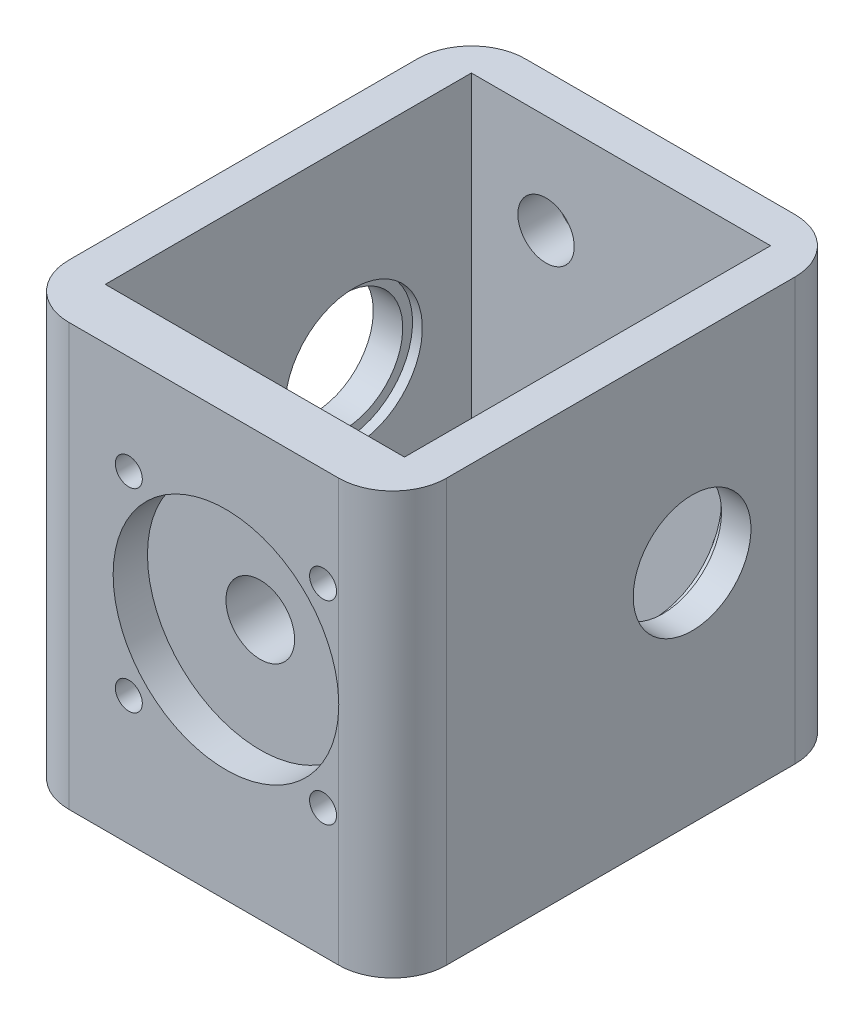
SolidWorks part; units mm, degrees
note: The reader was unsure of these and kept them because the rebuilt part matched: shared geometry of "Sketch4<3>", "Sketch4<4>", "Sketch4<5>", "Sketch6<3>", "Sketch6<4>".
ref_plane "Front Plane" through (0, 0, 0) normal (0, 0, 1) x (1, 0, 0)
ref_plane "Top Plane" through (0, 0, 0) normal (0, 1, 0) x (1, 0, 0)
ref_plane "Right Plane" through (0, 0, 0) normal (1, 0, 0) x (0, 0, -1)
sketch "Sketch1" plane through (0, 0, 0) normal (0, 1, 0) x (1, 0, 0)
  line L0 (-18, -30.53) -> (18, -30.53) construction
  line L1 (-3, -3.58) -> (3, -3.58) construction
  line L2 (-3, -3.58) -> (-3, -27.32) construction
  line L4 (3, -3.58) -> (3, -27.32) construction
  line L5 (-11, -27.32) -> (11, -27.32) construction
  line L6 (-11, -27.32) -> (-11, -30.53) construction
  line L8 (11, -27.32) -> (11, -30.53) construction
  line L13 (-6.58, 10.16) -> (-10.36, 10.16) construction
  line L14 (-10.16, -6.58) -> (10.16, -6.58) construction
  line L15 (-10.16, -6.58) -> (-10.16, -10.36) construction
  line L16 (-10.16, -10.36) -> (10.16, -10.36) construction
  line L17 (10.16, -6.58) -> (10.16, -10.36) construction
  line L18 (6.22, -10.36) -> (-6.22, -10.36) construction
  line L19 (6.22, -10.36) -> (6.22, -16.71) construction
  line L20 (6.22, -16.71) -> (-6.22, -16.71) construction
  line L21 (-6.22, -10.36) -> (-6.22, -16.71) construction
  line L22 (-6.58, 10.16) -> (-6.58, -10.16) construction
  line L23 (-6.58, -10.16) -> (-10.36, -10.16) construction
  line L24 (-10.36, 10.16) -> (-10.36, -10.16) construction
  line L25 (-10.36, -6.22) -> (-16.71, -6.22) construction
  line L26 (-10.36, -6.22) -> (-10.36, 6.22) construction
  line L27 (-10.36, 6.22) -> (-16.71, 6.22) construction
  line L28 (-16.71, -6.22) -> (-16.71, 6.22) construction
  line L37 (6.58, -10.16) -> (10.36, -10.16) construction
  line L38 (6.58, -10.16) -> (6.58, 10.16) construction
  line L39 (6.58, 10.16) -> (10.36, 10.16) construction
  line L40 (10.36, -10.16) -> (10.36, 10.16) construction
  line L41 (10.36, 6.22) -> (16.71, 6.22) construction
  line L42 (10.36, 6.22) -> (10.36, -6.22) construction
  line L43 (10.36, -6.22) -> (16.71, -6.22) construction
  line L44 (16.71, 6.22) -> (16.71, -6.22) construction
  line L45 (-18.51, -6) -> (-21.71, -6) construction
  line L46 (-6.8, -17.71) -> (6.8, -17.71) construction
  line L47 (-6.8, -17.71) -> (-6.8, -18.51) construction
  line L48 (-6.8, -18.51) -> (6.8, -18.51) construction
  line L49 (6.8, -17.71) -> (6.8, -18.51) construction
  line L50 (6, -18.51) -> (-6, -18.51) construction
  line L51 (6, -18.51) -> (6, -21.71) construction
  line L52 (6, -21.71) -> (-6, -21.71) construction
  line L53 (-6, -18.51) -> (-6, -21.71) construction
  line L54 (10.16, 6.58) -> (10.16, 10.36)
  line L55 (10.16, 6.58) -> (-10.16, 6.58)
  line L56 (-10.16, 6.58) -> (-10.16, 10.36)
  line L57 (10.16, 10.36) -> (-10.16, 10.36)
  line L58 (-6.22, 10.36) -> (-6.22, 16.71)
  line L59 (-6.22, 10.36) -> (6.22, 10.36)
  line L60 (6.22, 10.36) -> (6.22, 16.71)
  line L61 (-6.22, 16.71) -> (6.22, 16.71)
  line L62 (-18.51, -6) -> (-18.51, 6) construction
  line L63 (-18.51, 6) -> (-21.71, 6) construction
  line L64 (-21.71, -6) -> (-21.71, 6) construction
  line L65 (-17.71, 6.8) -> (-18.51, 6.8) construction
  line L66 (-17.71, 6.8) -> (-17.71, -6.8) construction
  line L67 (-17.71, -6.8) -> (-18.51, -6.8) construction
  line L68 (-18.51, 6.8) -> (-18.51, -6.8) construction
  line L77 (18.51, 6) -> (21.71, 6) construction
  line L78 (18.51, 6) -> (18.51, -6) construction
  line L79 (18.51, -6) -> (21.71, -6) construction
  line L80 (21.71, 6) -> (21.71, -6) construction
  line L81 (17.71, -6.8) -> (18.51, -6.8) construction
  line L82 (17.71, -6.8) -> (17.71, 6.8) construction
  line L83 (17.71, 6.8) -> (18.51, 6.8) construction
  line L84 (18.51, -6.8) -> (18.51, 6.8) construction
  line L85 (-6, 18.51) -> (-6, 21.71)
  line L86 (-6, 18.51) -> (6, 18.51)
  line L87 (6, 18.51) -> (6, 21.71)
  line L88 (-6, 21.71) -> (6, 21.71)
  line L89 (6.8, 17.71) -> (6.8, 18.51)
  line L90 (6.8, 17.71) -> (-6.8, 17.71)
  line L91 (-6.8, 17.71) -> (-6.8, 18.51)
  line L92 (6.8, 18.51) -> (-6.8, 18.51)
  line L93 (13.99, 6) -> (17.19, 6) construction
  line L94 (17.19, 6) -> (17.19, -6) construction
  line L95 (13.99, -6) -> (17.19, -6) construction
  line L96 (13.99, 6) -> (13.99, -6) construction
  line L97 (13.19, -6.8) -> (13.99, -6.8) construction
  line L98 (13.99, -6.8) -> (13.99, 6.8) construction
  line L99 (13.19, 6.8) -> (13.99, 6.8) construction
  line L100 (13.19, -6.8) -> (13.19, 6.8) construction
  line L101 (0, 0) -> (0, 17.1945) construction
  line L102 (-13.19, -6.8) -> (-13.19, 6.8) construction
  line L103 (-13.19, 6.8) -> (-13.99, 6.8) construction
  line L104 (-13.99, -6.8) -> (-13.99, 6.8) construction
  line L105 (-13.19, -6.8) -> (-13.99, -6.8) construction
  line L106 (-13.99, 6) -> (-13.99, -6) construction
  line L107 (-13.99, -6) -> (-17.19, -6) construction
  line L108 (-17.19, 6) -> (-17.19, -6) construction
  line L109 (-13.99, 6) -> (-17.19, 6) construction
  line L110 (-16, 16) -> (16, 16) construction
  circle A0 centre (0, 0) radius 4 construction
  circle A1 centre (8, 0) radius 1.85 construction
  circle A2 centre (5.6569, -5.6569) radius 1.85 construction
  circle A3 centre (0, -8) radius 1.85 construction
  circle A4 centre (-5.6569, -5.6569) radius 1.85 construction
  circle A5 centre (-8, 0) radius 1.85 construction
  circle A6 centre (-5.6569, 5.6569) radius 1.85 construction
  circle A7 centre (0, 8) radius 1.85 construction
  circle A8 centre (5.6569, 5.6569) radius 1.85 construction
  point P9 (0, -3.58)
  point P10 (0, -27.32)
  point P13 (0, -30.53)
  point P22 (0, -16.71)
  point P23 (0, -6.58)
  point P51 (0, 0)
  point P70 (0, 0)
  point P76 (0, -21.71)
  point P77 (0, -17.71)
  point P139 (0, 16)
  dimension "D13" = 8
  dimension "D14" = 3.7
  dimension "D1" = 36
  dimension "D2" = 22
  dimension "D3" = 6
  dimension "D4" = 3.21
  dimension "D5" = 26.95
  dimension "D6" = 3.58
  dimension "D7" = 3.78
  dimension "D8" = 6.35
  dimension "D9" = 20.32
  dimension "D10" = 12.44
  dimension "D11" = 20.17
  dimension "D12" = 4
  dimension "D15" = 8
  dimension "D17" = 0.8
  dimension "D18" = 3.2
  dimension "D19" = 13.6
  dimension "D20" = 12
  dimension "D21" = 1
  dimension "D23" = 19.77
  dimension "D24" = 16
  dimension "D25" = 16
  dimension "D22" = 2
  dimension "D16" = 8
sketch "Sketch3" plane through (0, 0, 0) normal (0, 1, 0) x (1, 0, 0)
  line L0 (-18, -30.53) -> (18, -30.53) construction
  line L1 (-16.01, 16) -> (11.49, 16)
  line L2 (-21.51, 10.5) -> (-21.51, -25.03)
  line L3 (-16.01, -30.53) -> (11.49, -30.53)
  line L4 (16.99, 10.5) -> (16.99, -25.03)
  line L7 (-16, 16) -> (16, 16) construction
  line L10 (13.99, -6.8) -> (13.99, 6.8) construction
  line L11 (-13.99, -6.8) -> (-13.99, 6.8) construction
  arc A0 (11.49, 16) -> (16.99, 10.5) centre (11.49, 10.5) cw
  arc A1 (11.49, -30.53) -> (16.99, -25.03) centre (11.49, -25.03) ccw
  arc A2 (-21.51, -25.03) -> (-16.01, -30.53) centre (-16.01, -25.03) ccw
  arc A3 (-16.01, 16) -> (-21.51, 10.5) centre (-16.01, 10.5) ccw
  dimension "D3" = 5.5
  dimension "D2" = 3
  dimension "D1" = 7.52
extrude "Boss-Extrude1" add sketch "Sketch3" along normal blind 20 and the other way blind 23
sketch "Sketch5" plane through (0, 20, 0) normal (0, 1, 0) x (1, 0, 0)
  line L0 (-21.51, 10.5) -> (-21.51, -25.03) construction
  line L1 (-17.51, 12) -> (12.99, 12)
  line L2 (-17.51, 12) -> (-17.51, -25.32)
  line L3 (-17.51, -25.32) -> (12.99, -25.32)
  line L4 (12.99, 12) -> (12.99, -25.32)
  line L5 (-11, -27.32) -> (11, -27.32) construction
  line L6 (-16, 16) -> (16, 16) construction
  line L7 (16.99, -25.03) -> (16.99, 10.5) construction
  dimension "D1" = 4
  dimension "D2" = 2
  dimension "D3" = 4
  dimension "D4" = 4
extrude "Cut-Extrude1" cut sketch "Sketch5" against normal offset from surface (40 mm away) 3 up to face at (-2.26, -23, 7.265)
sketch "Sketch4" plane through (0, 0, 25.32) normal (0, 0, 1) x (1, 0, 0)
  line L0 (-11.0781, 3.0864) -> (-17.51, -20)
  line L1 (-9.9, -9.9) -> (9.9, -9.9) construction
  line L2 (-9.9, -9.9) -> (-9.9, 9.9) construction
  line L3 (-9.9, 9.9) -> (9.9, 9.9) construction
  line L4 (9.9, -9.9) -> (9.9, 9.9) construction
  line L5 (-9.9, -9.9) -> (9.9, 9.9) construction
  line L6 (-9.9, 9.9) -> (9.9, -9.9) construction
  line L7 (11.4695, 0.8369) -> (12.99, -20)
  line L8 (-17.51, -20) -> (12.99, -20) construction
  line L9 (-17.51, -20) -> (12.99, -20)
  circle A0 centre (0, 0) radius 11.5
  circle A1 centre (9.9, -9.9) radius 1.375
  circle A2 centre (9.9, 9.9) radius 1.375
  circle A3 centre (-9.9, 9.9) radius 1.375
  circle A4 centre (-9.9, -9.9) radius 1.375
  circle A5 centre (0, 0) radius 3.5
  circle A6 centre (0, 0) radius 6
  dimension "D1" = 2.75
  dimension "D4" = 23
  dimension "D5" = 7
  dimension "D6" = 12
  dimension "D2" = 9.9
  dimension "D3" = 9.9
extrude "Boss-Extrude2" add sketch "Sketch4" against normal up to vertex (6.81 mm away) contours A0 L0 L9 L7 A4 A1 | A0 | A4 | A1 | A6 A5 | A5 up to point (6.8, 0, 18.51)
extrude "Cut-Extrude2" cut sketch "Sketch4<3>" against normal up to surface and the other way through all contours A3 | A4 | A2 | A1 | A5 up to face at (-0.7957, -6.6488, 18.51)
sketch "Sketch4<3>" plane through (0, 0, 25.32) normal (0, 0, 1) x (1, 0, 0) same geometry as "Sketch4"
extrude "Cut-Extrude3" cut sketch "Sketch4<4>" along normal blind 3.5 from surface at -6.81 contours A6 A5 starting at face at (-11.275, -9.9, 18.51)
sketch "Sketch4<4>" plane through (0, 0, 25.32) normal (0, 0, 1) x (1, 0, 0) same geometry as "Sketch4"
extrude "Cut-Extrude4" cut sketch "Sketch4<5>" against normal blind 3.5 from surface at 5.21 contours A0 A6 | A6 A5 starting at face at (-11.275, -9.9, 30.53)
sketch "Sketch4<5>" plane through (0, 0, 25.32) normal (0, 0, 1) x (1, 0, 0) same geometry as "Sketch4"
sketch "Sketch6" plane through (-21.51, 0, 0) normal (-1, 0, 0) x (0, 0, 1)
  circle A0 centre (0, 0) radius 6
  circle A1 centre (0, 0) radius 7
  dimension "D1" = 12
  dimension "D2" = 14
extrude "Cut-Extrude5" cut sketch "Sketch6" against normal through all both and the other way through all contours A0
extrude "Cut-Extrude6" cut sketch "Sketch6<3>" along normal blind 1 from surface at -4 starting at face at (-17.51, 0, 6)
sketch "Sketch6<3>" plane through (-21.51, 0, 0) normal (-1, 0, 0) x (0, 0, 1) same geometry as "Sketch6"
extrude "Cut-Extrude7" cut sketch "Sketch6<4>" against normal blind 1 from surface at -34.5 starting at face at (12.99, 0, -6)
sketch "Sketch6<4>" plane through (-21.51, 0, 0) normal (-1, 0, 0) x (0, 0, 1) same geometry as "Sketch6"
sketch "Sketch7" plane through (0, -20, 0) normal (0, 1, 0) x (1, 0, 0)
  circle A2 centre (5.6569, -5.6569) radius 1.85 construction
  circle A3 centre (0, -8) radius 1.85 construction
  circle A4 centre (-5.6569, -5.6569) radius 1.85 construction
  circle A5 centre (-8, 0) radius 1.85 construction
  circle A6 centre (-5.6569, 5.6569) radius 1.85 construction
  circle A7 centre (0, 8) radius 1.85 construction
  circle A8 centre (5.6569, 5.6569) radius 1.85 construction
  circle A9 centre (0, 0) radius 4 construction
  circle A10 centre (8, 0) radius 1.85 construction
  circle A11 centre (5.6569, -5.6569) radius 1.85
  circle A12 centre (0, -8) radius 1.85
  circle A13 centre (-5.6569, -5.6569) radius 1.85
  circle A14 centre (-8, 0) radius 1.85
  circle A15 centre (-5.6569, 5.6569) radius 1.85
  circle A16 centre (0, 8) radius 1.85
  circle A17 centre (5.6569, 5.6569) radius 1.85
  circle A18 centre (0, 0) radius 4
  circle A19 centre (8, 0) radius 1.85
extrude "Cut-Extrude8" cut sketch "Sketch7" against normal through all
sketch "Sketch8" plane through (0, 0, -12) normal (0, 0, 1) x (1, 0, 0)
  circle A0 centre (-9.9, 9.9) radius 2.875
  circle A2 centre (9.9, 9.9) radius 2.875
  circle A3 centre (-9.9, -9.9) radius 2.875
  circle A4 centre (9.9, -9.9) radius 2.875
  circle A5 centre (-9.9, 9.9) radius 1.375 construction
  dimension "D1" = 1.5
extrude "Cut-Extrude9" cut sketch "Sketch8" against normal through all
equation "\"CON\"= 3"
equation "\"D2@Sketch3\"=\"CON\""
equation "\"D1@Sketch3\"=10.52-\"CON\""
